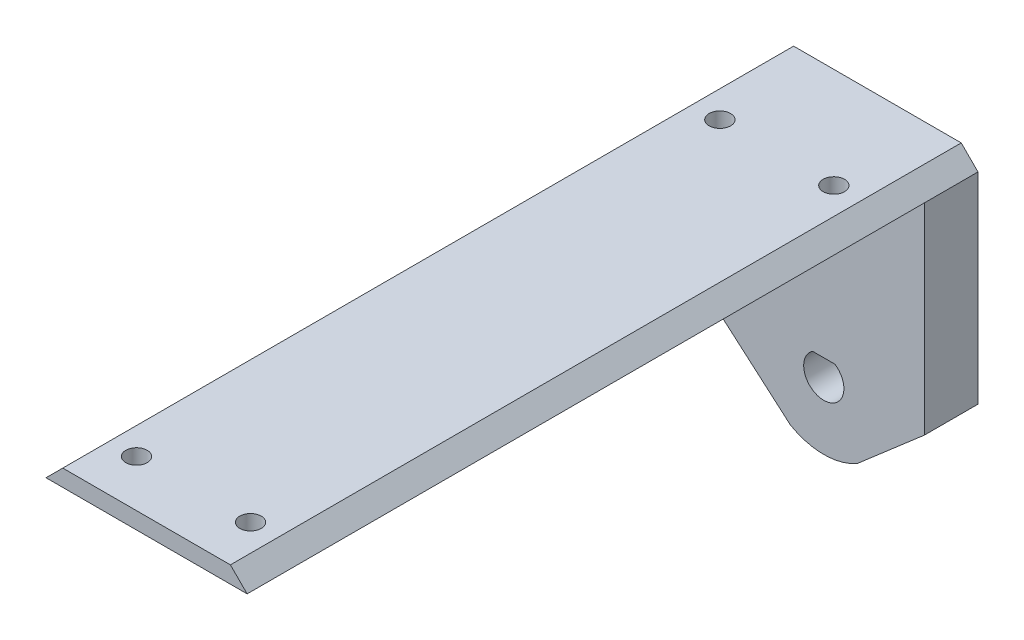
SolidWorks part; units mm, degrees
note: The reader was unsure of these and kept them because the rebuilt part matched: shared geometry of "Sketch1<5>".
material "ABS"
ref_plane "Front Plane" through (0, 0, 0) normal (0, 0, 1) x (1, 0, 0)
ref_plane "Top Plane" through (0, 0, 0) normal (0, 1, 0) x (1, 0, 0)
ref_plane "Right Plane" through (0, 0, 0) normal (1, 0, 0) x (0, 0, -1)
sketch "Sketch1" plane through (0, 0, 0) normal (0, 0, 1) x (1, 0, 0)
  line L0 (0, 0) -> (0, -7) construction
  line L1 (5, -15.6603) -> (-5, -15.6603) construction
  line L2 (15, 23) -> (-15, 23)
  line L3 (15, -7) -> (-15, -7) construction
  line L4 (15, -7) -> (15, 23)
  line L5 (-15, -7) -> (-15, 23)
  line L6 (15, -7) -> (5, -15.6603)
  line L7 (-5, -15.6603) -> (-15, -7)
  line L8 (15, 23) -> (15, 25.5) construction
  line L9 (15, 25.5) -> (-15, 25.5) construction
  line L10 (-15, 25.5) -> (-15, 23) construction
  line L11 (-15, 23) -> (-12.5, 25.5)
  line L12 (15, 23) -> (12.5, 25.5)
  line L13 (-12.5, 25.5) -> (12.5, 25.5)
  line L14 (1.6583, -4.5) -> (-1.6583, -4.5)
  circle A1 centre (0, -7) radius 10 construction
  arc A2 (-1.6583, -4.5) -> (1.6583, -4.5) centre (0, -7) ccw
  arc A3 (5, -15.6603) -> (-5, -15.6603) centre (0, -7) cw
  point P1 (0, -7)
  point P6 (0, -15.6603)
  dimension "D1" = 30
  dimension "D3" = 20
  dimension "D4" = 6
  dimension "D5" = 10
  dimension "D2" = 7
  dimension "D6" = 30
  dimension "D7" = 2.5
  dimension "D8" = 45
  dimension "D9" = 45
  dimension "D10" = 2.5
extrude "Boss-Extrude1" add sketch "Sketch1" along normal blind 8
extrude "Boss-Extrude3" add sketch "Sketch1<5>" along normal blind 109 contours L13 L11 L2 L12
sketch "Sketch1<5>" plane through (0, 0, 0) normal (0, 0, 1) x (1, 0, 0) same geometry as "Sketch1"
hole_wizard "M3 Clearance Slot1" positions "Sketch5" profile "Sketch4" size "M3" standard "ANSI Metric" slot yes end condition through all
sketch "Sketch5" plane through (0, 25.5, 0) normal (0, 1, 0) x (1, 0, 0)
  line L4 (-8.5, 0) -> (-8.5, -109) construction
  line L5 (-12.5, 0) -> (12.5, 0) construction
  line L6 (-12.5, -109) -> (12.5, -109) construction
  line L8 (-12.5, -109) -> (-12.5, 0) construction
  line L9 (8.5, 0) -> (8.5, -109) construction
  line L11 (12.5, -109) -> (12.5, 0) construction
  line L12 (-12.5, -102) -> (12.5, -102) construction
  line L14 (-12.5, -15) -> (12.5, -15) construction
  point P0 (-8.5, -15)
  point P4 (8.5, -15)
  point P6 (-8.5, -102)
  point P8 (8.5, -102)
  dimension "D1" = 4
  dimension "D2" = 4
  dimension "D3" = 7
  dimension "D4" = 15
sketch "Sketch4" plane through (-8.5, 25.5, 15) normal (1, 0, 0) x (0, 0, 1)
  line L0 (0, 0) -> (0, 42.5)
  line L1 (0, 42.5) -> (1.6, 42.5)
  line L2 (1.6, 42.5) -> (1.6, 0)
  line L5 (1.6, 0) -> (0, 0)
  line L11 (0, -6.35) -> (0, 107.95) construction
  dimension "Thru Hole Dia." = 3.2
  dimension "Thru Hole Depth" = 42.5
